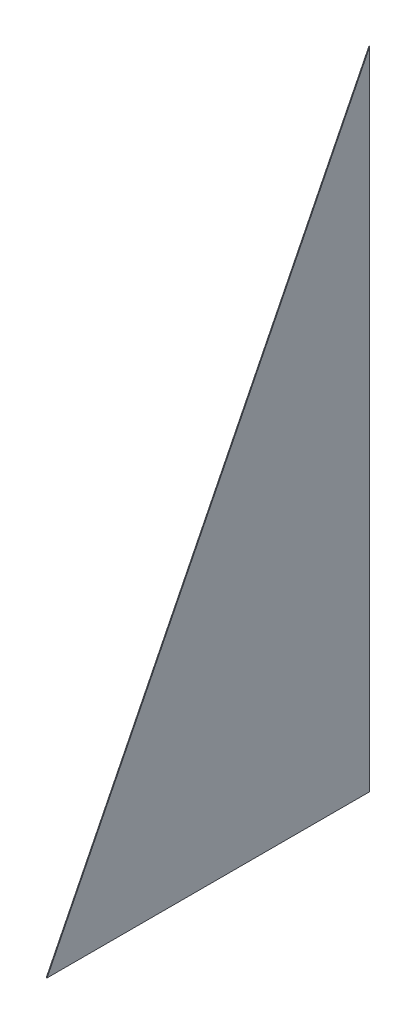
SolidWorks part; units mm, degrees
ref_plane "Front Plane" through (0, 0, 0) normal (0, 0, 1) x (1, 0, 0)
ref_plane "Top Plane" through (0, 0, 0) normal (0, 1, 0) x (1, 0, 0)
ref_plane "Right Plane" through (0, 0, 0) normal (1, 0, 0) x (0, 0, -1)
sketch "Sketch1" plane through (0, 0, 0) normal (1, 0, 0) x (0, 0, -1)
  line L0 (0, 0) -> (0, 800)
  line L1 (0, 800) -> (-400, 0)
  line L2 (-400, 0) -> (0, 0)
  dimension "D1" = 800
  dimension "D2" = 400
extrude "Boss-Extrude1" add sketch "Sketch1" along normal blind 1
